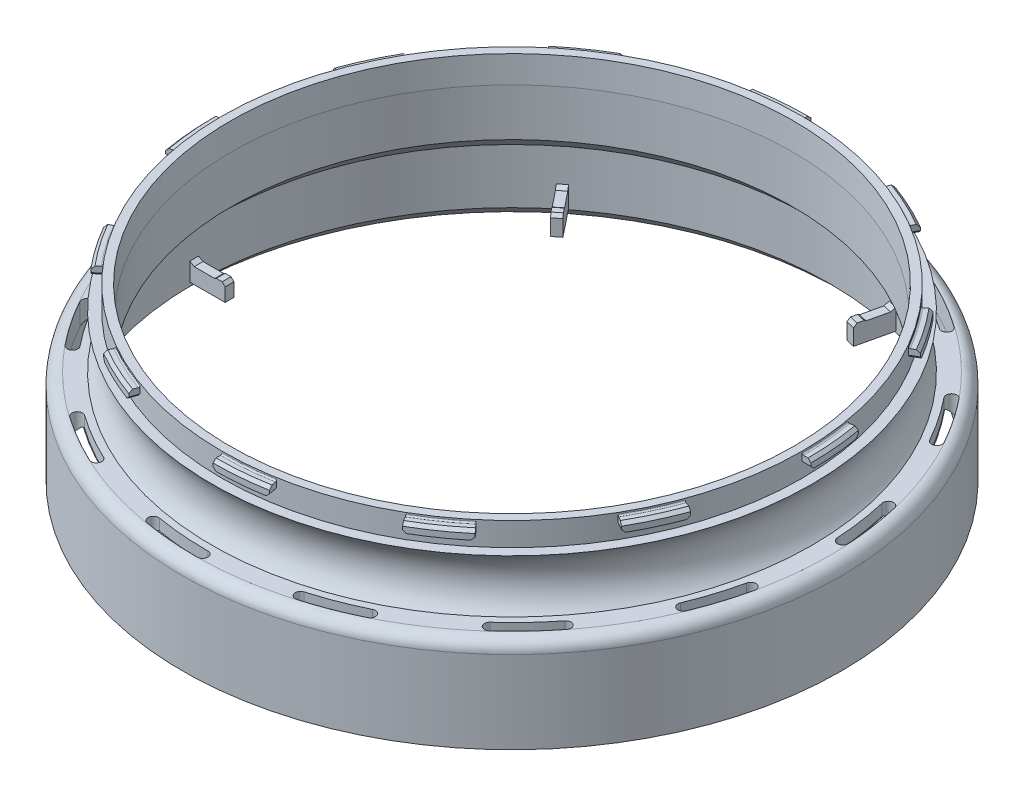
SolidWorks part; units mm, degrees
ref_plane "Front Plane" through (0, 0, 0) normal (0, 0, 1) x (1, 0, 0)
ref_plane "Top Plane" through (0, 0, 0) normal (0, 1, 0) x (1, 0, 0)
ref_plane "Right Plane" through (0, 0, 0) normal (1, 0, 0) x (0, 0, -1)
sketch "Locking slides" plane through (0, 0, 0) normal (0, 0, 1) x (1, 0, 0)
  line L0 (-52.5, 5.3) -> (-48, 5.3)
  line L1 (-51, 3.8) -> (-48, 3.8)
  line L2 (-51.4501, 8.7071) -> (-49.9501, 8.7071) construction
  line L3 (-54, 5.683) -> (-53.25, 5.25)
  line L6 (-48, 4.9) -> (-48, 2.15)
  line L7 (-48, 2.15) -> (-54, 2.15)
  line L9 (-52.5, 5.3) -> (-52.5, 2)
  line L12 (-51, 3.8) -> (-51, 2)
  line L13 (-51, 2) -> (-52.5, 2)
  line L14 (-48, 5.3) -> (-48, 3.8)
  line L15 (-51, 2) -> (-48, 2)
  line L16 (-48, 2) -> (-48, 3.8)
  line L17 (-54, 5.683) -> (-54, 2.15)
  line L18 (-48.5, 5.4) -> (-49.5, 5.4)
  line L19 (-49.5, 5.4) -> (-49.7598, 5.25)
  line L20 (-49.7598, 5.25) -> (-53.25, 5.25)
  line L21 (-48, 4.9) -> (-48.5, 5.4)
  line L22 (-49.5, 3.8) -> (-49.5, 3.5) construction
  line L23 (-49.9501, 8.7071) -> (-49.8501, 8.7071) construction
  line L25 (0, 21.25) -> (-54, 21.25) construction
  line L26 (0, 0) -> (0, 42.5) construction
  line L27 (-49.9501, 33.7929) -> (-49.8501, 33.7929) construction
  line L28 (-49.5, 38.7) -> (-49.5, 39) construction
  line L29 (-51.4501, 33.7929) -> (-49.9501, 33.7929) construction
  line L30 (-48, 37.6) -> (-48.5, 37.1)
  line L31 (-49.7598, 37.25) -> (-53.25, 37.25)
  line L32 (-49.5, 37.1) -> (-49.7598, 37.25)
  line L33 (-48.5, 37.1) -> (-49.5, 37.1)
  line L34 (-54, 36.817) -> (-54, 40.35)
  line L35 (-48, 40.5) -> (-48, 38.7)
  line L36 (-51, 40.5) -> (-48, 40.5)
  line L37 (-48, 37.2) -> (-48, 38.7)
  line L38 (-51, 40.5) -> (-52.5, 40.5)
  line L39 (-51, 38.7) -> (-51, 40.5)
  line L40 (-52.5, 37.2) -> (-52.5, 40.5)
  line L41 (-48, 40.35) -> (-54, 40.35)
  line L42 (-48, 37.6) -> (-48, 40.35)
  line L43 (-54, 36.817) -> (-53.25, 37.25)
  line L44 (-51, 38.7) -> (-48, 38.7)
  line L45 (-52.5, 37.2) -> (-48, 37.2)
  point P4 (-48, 5.4)
  point P30 (0, 0)
  point P54 (-48, 37.1)
sketch "Body outline" plane through (0, 0, 0) normal (0, 0, 1) x (1, 0, 0)
  line L0 (0, 0) -> (-56, 0)
  line L1 (-56, 0) -> (-56, 14)
  line L5 (-54, 2) -> (0, 2)
  line L6 (0, 2) -> (0, 0)
  line L7 (-54, 2) -> (-54, 12.2322)
  line L10 (-52.2322, 14) -> (-54, 12.2322)
  line L12 (-54, 16) -> (-51, 16)
  line L13 (-47.7, 16.4716) -> (-50.1716, 14)
  line L16 (-52.2322, 14) -> (-50.1716, 14)
  line L21 (-54, 29.7678) -> (-52.2322, 28)
  line L22 (-54, 2) -> (-56, 0)
  line L27 (-54, 40.5) -> (-56, 39.7)
  line L32 (0, 0) -> (0, 30.814) construction
  line L33 (-49.55, 28.5) -> (-50.3, 28.5)
  line L34 (-50.8, 28) -> (-50.8, 27)
  line L38 (-56, 39.7) -> (-56, 27.8)
  line L39 (-49.5, 26.5) -> (-49.5, 25.5)
  line L40 (-52.2322, 28) -> (-51, 28)
  line L41 (-51, 28) -> (-51, 26.5)
  line L46 (-51, 26.5) -> (-49.5, 26.5)
  line L47 (-47.7, 16.4716) -> (-47.7, 24.5284)
  line L51 (-49.2, 16) -> (-49.2, 20.5) construction
  line L52 (-50.8, 27) -> (-49.3, 27)
  line L53 (0, 40.5) -> (0, 42.5)
  line L54 (-54, 40.5) -> (0, 40.5)
  line L55 (-47.7, 24.5284) -> (-47.8788, 29)
  line L56 (-53.2, 42.5) -> (0, 42.5)
  line L57 (-51, 25) -> (-50, 25)
  line L58 (-54, 40.5) -> (-54, 29.7678)
  line L59 (-53.2, 25) -> (-51, 25)
  line L60 (-49.3, 27) -> (-49.3, 25)
  line L61 (-49.5, 25.5) -> (-50, 25)
  line L62 (-50.3, 28.5) -> (-50.8, 28)
  line L63 (-50, 25) -> (-49.3, 25)
  line L64 (-49.3, 27) -> (-49.3, 28.5)
  line L66 (-49.3, 28.75) -> (-49.3, 29)
  line L67 (-49.3, 29) -> (-47.8788, 29)
  line L68 (-49.3, 28.75) -> (-49.3, 28.5)
  line L69 (-51, 26.5) -> (-51, 25)
  line L70 (-27, 2) -> (-27, 5.3) construction
  line L71 (0, 41.8) -> (-55.052, 41.8) construction
  arc A0 (-56, 14) -> (-54, 16) centre (-54, 14) cw
  arc A5 (-51, 25) -> (-51, 16) centre (-55.725, 20.5) cw
  arc A7 (-56, 27.8) -> (-53.2, 25) centre (-53.2, 27.8) ccw
  arc A8 (-56, 39.7) -> (-53.2, 42.5) centre (-53.2, 39.7) cw
  arc A9 (-49.3, 28.75) -> (-49.55, 28.5) centre (-49.55, 28.75) cw
  point P20 (-49.5, 25)
  point P22 (-50.8, 28.5)
  point P35 (0, 0)
revolve "Revolve body" add sketch "Body outline" angle 360 about L32 region at (-52.0895, 14.6318, 0)
extrude "Boss-Extrude locking slide" add sketch "Locking slides" along normal mid plane 1.5 contours L9 L20 L3 L17 L7 | L6 L21 L0 L19 L20 L9 L7 L12 L1 | L0 L21 L18 L19 | L1 L12 L7 L6 region at (-49.019, 5.348, 0) region at (-50.6678, 4.1005, 0) region at (-53.2669, 3.7572, 0) region at (-49.5, 2.975, 0)
chamfer "Chamfer locking slide" distance 0.45 angle 45 3 edges at (-50.9974, 2.15, 0.75) (-48, 2.15, 0) (-50.9974, 2.15, -0.75)
pattern_circular "CirPattern locking slides" count 7 over 360 about axis through (0, 0, 0) along (0, 1, 0) of "Boss-Extrude locking slide" reverse direction yes
sketch "Locking shafts" plane through (0, 0, 0) normal (0, 0, 1) x (1, 0, 0)
  line L0 (-51, 2) -> (-51, 3.8)
  line L2 (-51, 3.8) -> (-51.25, 3.8)
  line L3 (-50.4109, 5.3) -> (-51.25, 4.3)
  line L4 (-51, 2) -> (-49.5, 2)
  line L5 (-51.25, 4.3) -> (-51.25, 3.8)
  line L6 (-50.4109, 5.3) -> (-49.5, 5.3)
  line L7 (-49.5, 40.5) -> (-49.5, 37.2)
  line L8 (-49.5, 5.3) -> (-49.5, 2)
  line L9 (-51.25, 3.8) -> (-51.25, 3.5) construction
  line L10 (-49.5, 37.2) -> (-50.4109, 37.2)
  line L11 (-50.4109, 37.2) -> (-51.25, 38.2)
  line L12 (-51.25, 38.2) -> (-51.25, 38.7)
  line L13 (-51.25, 38.7) -> (-51, 38.7)
  line L14 (-51, 38.7) -> (-51, 40.5)
  line L15 (-51, 40.5) -> (-49.5, 40.5)
  line L17 (-51.25, 38.7) -> (-51.25, 39) construction
sketch "Locking clips" plane through (0, 0, 0) normal (0, 1, 0) x (1, 0, 0)
  line L11 (0, 0) -> (-53.7514, 5.1757) construction
  line L12 (0, 0) -> (-54, 0) construction
  line L14 (-53.5633, 7.1291) -> (-53.6975, 5.7356)
  line L15 (-53.6975, 5.7356) -> (-50.7092, 5.4478)
  line L16 (-53.5633, 7.1291) -> (-51.3426, 6.9153)
  line L17 (-46.4995, 5.8902) -> (-47.7934, 5.3555)
  line L18 (-46.7691, 3.0906) -> (-47.9372, 3.8624)
  line L19 (-53.9395, 3.2222) -> (-51.7188, 3.0084)
  line L20 (-53.8053, 4.6158) -> (-50.817, 4.328)
  line L21 (-53.9395, 3.2222) -> (-53.8053, 4.6158)
  arc A4 (-50.7092, 5.4478) -> (-47.7934, 5.3555) centre (-49.2721, 4.7444) cw
  arc A5 (-51.3426, 6.9153) -> (-46.4995, 5.8902) centre (-49.2721, 4.7444) cw
  arc A6 (-51.7188, 3.0084) -> (-46.7691, 3.0906) centre (-49.2721, 4.7444) ccw
  arc A7 (-50.817, 4.328) -> (-47.9372, 3.8624) centre (-49.2721, 4.7444) ccw
  point P60 (0, 0)
extrude "Boss-Extrude locking clip" [suppressed] add sketch "Locking clips" along normal up to vertex from vertex
fillet "Fillet locking clip" [suppressed] radius 0.75
pattern_circular "CirPattern locking clips" [suppressed] count 7 over 360 reverse direction yes of bodies 110
revolve "Revolve locking clamp" add sketch "Body outline<6>" angle 10 about L32 region at (-50.0115, 27.721, 0)
sketch "Body outline<6>" plane through (0, 0, 0) normal (0, 0, 1) x (1, 0, 0) same geometry as "Body outline"
chamfer "Chamfer locking clamp" distance 0.5 angle 45 2 edges at (-49.2896, 27, 8.6911) (-50.05, 27, 0)
pattern_circular "CirPattern locking clamps" count 12 over 360 of "Revolve locking clamp", "Chamfer locking clamp" reverse direction yes
sketch "Air vents" plane through (0, 0, 0) normal (0, 1, 0) x (1, 0, 0)
  line L0 (-54, 0) -> (-52.2, 0) construction
  line L1 (-51.719, 22.1402) -> (-45.7913, 19.5628) construction
  line L4 (-55.2095, 11.0697) -> (-48.8754, 9.7811) construction
  arc A0 (-52.7418, 11.5019) -> (-49.9454, 20.3708) centre (-0.8, 0) cw
  arc A1 (-50.9843, 11.1128) -> (-48.2826, 19.6815) centre (-0.8, 0) cw
  arc A2 (-49.9454, 20.3708) -> (-48.2826, 19.6815) centre (-49.114, 20.0261) cw
  arc A3 (-50.9843, 11.1128) -> (-52.7418, 11.5019) centre (-51.863, 11.3073) cw
extrude "Cut-Extrude air vent" cut sketch "Air vents" against normal up to surface (1.9077 mm away) from surface up to face at (54, 12.2322, 0) starting at face at (51, 16, 0)
pattern_circular "CirPattern air vents" count 14 over 360 about axis through (0, 0, 0) along (0, 1, 0) of "Cut-Extrude air vent" reverse direction yes
sketch "Locking cutaway"
  line L1 (64.5022, 29.3359) -> (26.0856, 29.3359)
  line L2 (64.5022, 29.3359) -> (64.5022, 13.2814)
  line L3 (64.5022, 13.2814) -> (26.0856, 13.2814)
  line L4 (26.0856, 29.3359) -> (26.0856, 13.2814)
extrude "Cut-Extrude locking slice" [suppressed] cut sketch "Locking cutaway" along normal through all flip side to cut
equation "\"D1@CirPattern locking clips\"= \"Locking shaft count@Enclosure master-1.Part\""
equation "\"D1@Revolve locking clamp\" = 120 / \"Locking clamp count@Enclosure master<1>.Part\""
equation "\"D1@CirPattern locking clamps\"=\"Locking clamp count@Enclosure master-1.Part\""
equation "\"D1@Chamfer locking clamp\"=\"D28@Body outline@Enclosure master-1.Part\"/2"
equation "\"D1@CirPattern air vents\"=\"Air hole count@Enclosure master-1.Part\""
equation "\"D1@Boss-Extrude locking slide\" = \"Base width@Locking slides@Enclosure master<1>.Part\""
equation "\"D1@CirPattern locking slides\"=\"Locking shaft count@Enclosure master-1.Part\""
